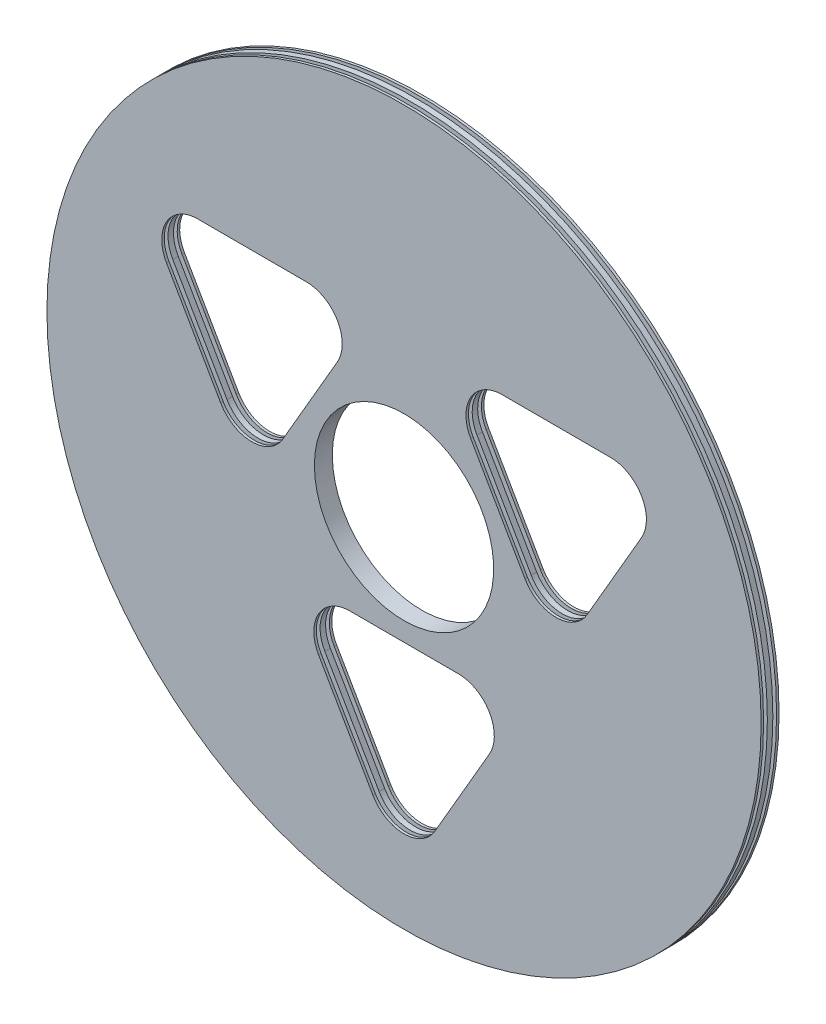
SolidWorks part; units mm, degrees
ref_plane "Спереди" through (0, 0, 0) normal (0, 0, 1) x (1, 0, 0)
ref_plane "Сверху" through (0, 0, 0) normal (0, 1, 0) x (1, 0, 0)
ref_plane "Справа" through (0, 0, 0) normal (1, 0, 0) x (0, 0, -1)
sketch "Эскиз1" plane through (0, 0, 0) normal (0, 0, 1) x (1, 0, 0)
  circle A0 centre (0, 0) radius 199.1381
extrude "Бобышка-Вытянуть1" add sketch "Эскиз1" along normal blind 10 contours A0
sketch "Эскиз2" plane through (0, 0, 0) normal (0, 0, -1) x (-1, 0, 0)
  line L0 (0, 0) -> (0, -268.0908) construction
  line L1 (-132.4605, 56.4033) -> (-102.0761, 3.9458)
  line L2 (17.3836, -142.9158) -> (47.6208, -90.3734)
  line L3 (30.2583, -60.3977) -> (-30.3634, -60.4827)
  line L4 (-47.6419, -90.507) -> (-17.2574, -142.9644)
  line L5 (-67.4351, 3.9944) -> (-37.1978, 56.5369)
  line L6 (-54.5604, 86.5125) -> (-115.1821, 86.4276)
  line L7 (115.077, 86.5125) -> (54.4552, 86.4276)
  line L8 (37.1768, 56.4033) -> (67.5613, 3.9458)
  line L9 (102.2023, 3.9944) -> (132.4395, 56.5369)
  circle A0 centre (0, 0) radius 50
  circle A1 centre (0, -97.9402) radius 37.5 construction
  arc A2 (-17.2574, -142.9644) -> (17.3836, -142.9158) centre (0.0491, -132.9401) ccw
  arc A3 (-30.3634, -60.4827) -> (-47.6419, -90.507) centre (-30.3354, -80.4827) ccw
  arc A4 (30.2583, -60.3977) -> (47.6208, -90.3734) centre (30.2863, -80.3977) cw
  circle A5 centre (0, 0) radius 199.1381 construction
  arc A6 (-115.1821, 86.4276) -> (-132.4605, 56.4033) centre (-115.1541, 66.4276) ccw
  arc A7 (-37.1978, 56.5369) -> (-54.5604, 86.5125) centre (-54.5324, 66.5126) ccw
  arc A8 (-67.4351, 3.9944) -> (-102.0761, 3.9458) centre (-84.7696, 13.9701) cw
  circle A9 centre (-84.8187, 48.9701) radius 37.5 construction
  arc A10 (132.4395, 56.5369) -> (115.077, 86.5125) centre (115.105, 66.5126) ccw
  arc A11 (67.5613, 3.9458) -> (102.2023, 3.9944) centre (84.8677, 13.9701) ccw
  arc A12 (37.1768, 56.4033) -> (54.4552, 86.4276) centre (54.4833, 66.4276) cw
  circle A13 centre (84.8187, 48.9701) radius 37.5 construction
  dimension "D1" = 100
  dimension "D2" = 20
  dimension "D3" = 75
  dimension "D4" = 0.0491
  dimension "D5" = 60.3977
  dimension "D6" = 3
extrude "Вырез-Вытянуть1" cut sketch "Эскиз2" against normal blind 10
ref_axis "Ось1" through (0, 0, 0) along (0, 0, -1)
sketch "Эскиз4" plane through (0, 0, 0) normal (1, 0, 0) x (0, 0, -1)
  line L0 (-5, 199.2238) -> (-5, 38.4981) construction
  line L1 (-8.6134, 199.2238) -> (-6.5325, 199.2238)
  line L2 (-8.6134, 199.2238) -> (-8.6134, 53.5156)
  line L3 (-8.6134, 53.5156) -> (-6.5325, 53.5156)
  line L4 (-6.5325, 199.2238) -> (-6.5325, 53.5156)
  line L5 (0, -199.1381) -> (0, 199.1381) construction
  line L6 (-1.3866, 53.5156) -> (-3.4675, 53.5156)
  line L7 (-3.4675, 199.2238) -> (-3.4675, 53.5156)
  line L8 (-1.3866, 199.2238) -> (-3.4675, 199.2238)
  line L9 (-1.3866, 199.2238) -> (-1.3866, 53.5156)
  line L14 (-0.5, 0) -> (-17.8949, 0) construction
  dimension "D1" = 5
  dimension "D2" = 1.3866
  dimension "D3" = 3.4675
  dimension "D4" = 53.5156
  dimension "D5" = 199.2238
revolve "Вырез-Повернуть1" cut sketch "Эскиз4" angle 360 about L14
sketch "Эскиз5" plane through (0, 0, 10) normal (0, 0, 1) x (1, 0, 0)
  line L0 (0, 0) -> (0, 220.1725) construction
  line L1 (0, 0) -> (-285.0423, 0) construction
  line L2 (0, 0) -> (-10.9479, 224.9473) construction
  line L3 (0, 0) -> (-30.7455, 220.1725) construction
  line L4 (-8.6092, 176.8935) -> (-9.5827, 196.8968)
  line L6 (-27.2632, 195.2355) -> (-24.4935, 175.401)
  line L46 (176.8935, 8.6092) -> (196.8968, 9.5827)
  line L47 (195.2355, 27.2632) -> (175.401, 24.4935)
  line L48 (-171.8331, 30.5179) -> (-194.0925, 34.4712)
  line L49 (-196.4072, 16.8643) -> (-173.6062, 14.9065)
  line L51 (-187.7302, 60.1462) -> (-166.586, 53.3719)
  line L56 (-84.3258, 155.305) -> (-94.0641, 173.2401)
  line L58 (-47.7244, 170.4303) -> (-53.1561, 189.8278)
  line L59 (-70.0237, 184.2739) -> (-62.8368, 165.361)
  line L108 (30.5179, 171.8331) -> (34.4712, 194.0925)
  line L109 (16.8643, 196.4072) -> (14.9065, 173.6062)
  line L110 (60.1462, 187.7302) -> (53.3719, 166.586)
  line L111 (155.305, 84.3258) -> (173.2401, 94.0641)
  line L112 (170.4303, 47.7244) -> (189.8278, 53.1561)
  line L113 (184.2739, 70.0237) -> (165.361, 62.8368)
  line L114 (0, 0) -> (220.1725, 0) construction
  line L115 (0, 0) -> (224.9473, 10.9479) construction
  line L116 (0, 0) -> (220.1725, 30.7455) construction
  line L117 (8.6092, -176.8935) -> (9.5827, -196.8968)
  line L118 (27.2632, -195.2355) -> (24.4935, -175.401)
  line L119 (171.8331, -30.5179) -> (194.0925, -34.4712)
  line L120 (196.4072, -16.8643) -> (173.6062, -14.9065)
  line L121 (187.7302, -60.1462) -> (166.586, -53.3719)
  line L122 (84.3258, -155.305) -> (94.0641, -173.2401)
  line L123 (47.7244, -170.4303) -> (53.1561, -189.8278)
  line L124 (70.0237, -184.2739) -> (62.8368, -165.361)
  line L125 (0, 0) -> (0, -220.1725) construction
  line L126 (0, 0) -> (10.9479, -224.9473) construction
  line L127 (0, 0) -> (30.7455, -220.1725) construction
  line L128 (-176.8935, -8.6092) -> (-196.8968, -9.5827)
  line L129 (-195.2355, -27.2632) -> (-175.401, -24.4935)
  line L130 (-30.5179, -171.8331) -> (-34.4712, -194.0925)
  line L131 (-16.8643, -196.4072) -> (-14.9065, -173.6062)
  line L132 (-60.1462, -187.7302) -> (-53.3719, -166.586)
  line L133 (-155.305, -84.3258) -> (-173.2401, -94.0641)
  line L134 (-170.4303, -47.7244) -> (-189.8278, -53.1561)
  line L135 (-184.2739, -70.0237) -> (-165.361, -62.8368)
  line L136 (0, 0) -> (-220.1725, 0) construction
  line L137 (0, 0) -> (-224.9473, -10.9479) construction
  line L138 (0, 0) -> (-220.1725, -30.7455) construction
  arc A0 (-8.6092, 176.8935) -> (-24.4935, 175.401) centre (0, 0) ccw
  arc A3 (-9.5827, 196.8968) -> (-11.6979, 198.7961) centre (-11.5804, 196.7996) ccw
  arc A4 (-25.5389, 197.4956) -> (-27.2632, 195.2355) centre (-25.2824, 195.5121) ccw
  arc A64 (-171.8331, 30.5179) -> (-173.6062, 14.9065) centre (0, 3.0953) ccw
  arc A65 (-84.3258, 155.305) -> (-166.586, 53.3719) centre (0, 3.0953) ccw
  arc A66 (-47.7244, 170.4303) -> (-62.8368, 165.361) centre (0, 3.0953) ccw
  arc A68 (-194.0925, 34.4712) -> (-196.4149, 32.8317) centre (-194.4423, 32.502) ccw
  arc A69 (-198.2269, 19.0483) -> (-196.4072, 16.8643) centre (-196.2361, 18.857) ccw
  arc A72 (-189.0183, 62.6803) -> (-187.7302, 60.1462) centre (-187.1199, 62.0508) ccw
  arc A80 (-94.0641, 173.2401) -> (-96.7938, 174.0336) centre (-95.8217, 172.2858) ccw
  arc A83 (-53.1561, 189.8278) -> (-55.6409, 191.2089) centre (-55.0821, 189.2885) ccw
  arc A84 (-68.8455, 186.861) -> (-70.0237, 184.2739) centre (-68.1541, 184.9843) ccw
  arc A104 (176.8935, 8.6092) -> (170.5427, 47.7558) centre (0, 0) ccw
  arc A105 (-196.4149, 32.8317) -> (-198.2269, 19.0483) centre (0, 0) ccw
  arc A106 (-170.3315, 103.1693) -> (-189.0183, 62.6803) centre (0, 0) ccw
  arc A107 (-143.1036, 138.485) -> (-170.3315, 103.1693) centre (0, 0) ccw
  arc A108 (-108.6999, 166.8564) -> (-143.1036, 138.485) centre (0, 0) ccw
  arc A109 (-96.7938, 174.0336) -> (-108.6999, 166.8564) centre (0, 0) ccw
  arc A110 (-55.6409, 191.2089) -> (-68.8455, 186.861) centre (0, 0) ccw
  arc A111 (-9.6804, 198.9046) -> (-27.5412, 197.2263) centre (0, 0) ccw
  arc A112 (0, 199.14) -> (-198.2269, 19.0483) centre (0, 0) ccw
  arc A113 (-8.609, 176.8898) -> (-24.4893, 175.371) centre (0, 3.0953) ccw
  arc A189 (196.8968, 9.5827) -> (198.7961, 11.6979) centre (196.7996, 11.5804) ccw
  arc A190 (197.4956, 25.5389) -> (195.2355, 27.2632) centre (195.5121, 25.2824) ccw
  arc A191 (30.5179, 171.8331) -> (14.9065, 173.6062) centre (3.0953, 0) ccw
  arc A192 (165.361, 62.8368) -> (53.3719, 166.586) centre (3.0953, 0) ccw
  arc A193 (170.4303, 47.7244) -> (165.361, 62.8368) centre (3.0953, 0) ccw
  arc A194 (34.4712, 194.0925) -> (32.8317, 196.4149) centre (32.502, 194.4423) ccw
  arc A195 (19.0483, 198.2269) -> (16.8643, 196.4072) centre (18.857, 196.2361) ccw
  arc A196 (62.6803, 189.0183) -> (60.1462, 187.7302) centre (62.0508, 187.1199) ccw
  arc A197 (173.2401, 94.0641) -> (174.0336, 96.7938) centre (172.2858, 95.8217) ccw
  arc A198 (189.8278, 53.1561) -> (191.2089, 55.6409) centre (189.2885, 55.0821) ccw
  arc A199 (186.861, 68.8455) -> (184.2739, 70.0237) centre (184.9843, 68.1541) ccw
  arc A200 (32.8317, 196.4149) -> (19.0483, 198.2269) centre (0, 0) ccw
  arc A201 (103.1693, 170.3315) -> (62.6803, 189.0183) centre (0, 0) ccw
  arc A202 (138.485, 143.1036) -> (103.1693, 170.3315) centre (0, 0) ccw
  arc A203 (166.8564, 108.6999) -> (138.485, 143.1036) centre (0, 0) ccw
  arc A204 (174.0336, 96.7938) -> (166.8564, 108.6999) centre (0, 0) ccw
  arc A205 (191.2089, 55.6409) -> (174.0336, 96.7938) centre (0, 0) ccw
  arc A206 (198.9046, 9.6804) -> (191.2089, 55.6409) centre (0, 0) ccw
  arc A207 (199.14, 0) -> (19.0483, 198.2269) centre (0, 0) ccw
  arc A208 (176.8898, 8.609) -> (175.371, 24.4893) centre (3.0953, 0) ccw
  arc A209 (8.6092, -176.8935) -> (24.4935, -175.401) centre (0, 0) ccw
  arc A210 (9.5827, -196.8968) -> (11.6979, -198.7961) centre (11.5804, -196.7996) ccw
  arc A211 (25.5389, -197.4956) -> (27.2632, -195.2355) centre (25.2824, -195.5121) ccw
  arc A212 (171.8331, -30.5179) -> (173.6062, -14.9065) centre (0, -3.0953) ccw
  arc A213 (84.3258, -155.305) -> (166.586, -53.3719) centre (0, -3.0953) ccw
  arc A214 (47.7244, -170.4303) -> (62.8368, -165.361) centre (0, -3.0953) ccw
  arc A215 (194.0925, -34.4712) -> (196.4149, -32.8317) centre (194.4423, -32.502) ccw
  arc A216 (198.2269, -19.0483) -> (196.4072, -16.8643) centre (196.2361, -18.857) ccw
  arc A217 (189.0183, -62.6803) -> (187.7302, -60.1462) centre (187.1199, -62.0508) ccw
  arc A218 (94.0641, -173.2401) -> (96.7938, -174.0336) centre (95.8217, -172.2858) ccw
  arc A219 (53.1561, -189.8278) -> (55.6409, -191.2089) centre (55.0821, -189.2885) ccw
  arc A220 (68.8455, -186.861) -> (70.0237, -184.2739) centre (68.1541, -184.9843) ccw
  arc A221 (196.4149, -32.8317) -> (198.2269, -19.0483) centre (0, 0) ccw
  arc A222 (170.3315, -103.1693) -> (189.0183, -62.6803) centre (0, 0) ccw
  arc A223 (143.1036, -138.485) -> (170.3315, -103.1693) centre (0, 0) ccw
  arc A224 (108.6999, -166.8564) -> (143.1036, -138.485) centre (0, 0) ccw
  arc A225 (96.7938, -174.0336) -> (108.6999, -166.8564) centre (0, 0) ccw
  arc A226 (55.6409, -191.2089) -> (68.8455, -186.861) centre (0, 0) ccw
  arc A227 (9.6804, -198.9046) -> (27.5412, -197.2263) centre (0, 0) ccw
  arc A228 (0, -199.14) -> (198.2269, -19.0483) centre (0, 0) ccw
  arc A229 (8.609, -176.8898) -> (24.4893, -175.371) centre (0, -3.0953) ccw
  arc A230 (-176.8935, -8.6092) -> (-175.401, -24.4935) centre (0, 0) ccw
  arc A231 (-196.8968, -9.5827) -> (-198.7961, -11.6979) centre (-196.7996, -11.5804) ccw
  arc A232 (-197.4956, -25.5389) -> (-195.2355, -27.2632) centre (-195.5121, -25.2824) ccw
  arc A233 (-30.5179, -171.8331) -> (-14.9065, -173.6062) centre (-3.0953, 0) ccw
  arc A234 (-155.305, -84.3258) -> (-53.3719, -166.586) centre (-3.0953, 0) ccw
  arc A235 (-170.4303, -47.7244) -> (-165.361, -62.8368) centre (-3.0953, 0) ccw
  arc A236 (-34.4712, -194.0925) -> (-32.8317, -196.4149) centre (-32.502, -194.4423) ccw
  arc A237 (-19.0483, -198.2269) -> (-16.8643, -196.4072) centre (-18.857, -196.2361) ccw
  arc A238 (-62.6803, -189.0183) -> (-60.1462, -187.7302) centre (-62.0508, -187.1199) ccw
  arc A239 (-173.2401, -94.0641) -> (-174.0336, -96.7938) centre (-172.2858, -95.8217) ccw
  arc A240 (-189.8278, -53.1561) -> (-191.2089, -55.6409) centre (-189.2885, -55.0821) ccw
  arc A241 (-186.861, -68.8455) -> (-184.2739, -70.0237) centre (-184.9843, -68.1541) ccw
  arc A242 (-32.8317, -196.4149) -> (-19.0483, -198.2269) centre (0, 0) ccw
  arc A243 (-103.1693, -170.3315) -> (-62.6803, -189.0183) centre (0, 0) ccw
  arc A244 (-138.485, -143.1036) -> (-103.1693, -170.3315) centre (0, 0) ccw
  arc A245 (-166.8564, -108.6999) -> (-138.485, -143.1036) centre (0, 0) ccw
  arc A246 (-174.0336, -96.7938) -> (-166.8564, -108.6999) centre (0, 0) ccw
  arc A247 (-191.2089, -55.6409) -> (-186.861, -68.8455) centre (0, 0) ccw
  arc A248 (-198.9046, -9.6804) -> (-197.2263, -27.5412) centre (0, 0) ccw
  arc A249 (-199.14, 0) -> (-19.0483, -198.2269) centre (0, 0) ccw
  arc A250 (-176.8898, -8.609) -> (-175.371, -24.4893) centre (-3.0953, 0) ccw
  dimension "D2" = 4
  dimension "D3" = 4
